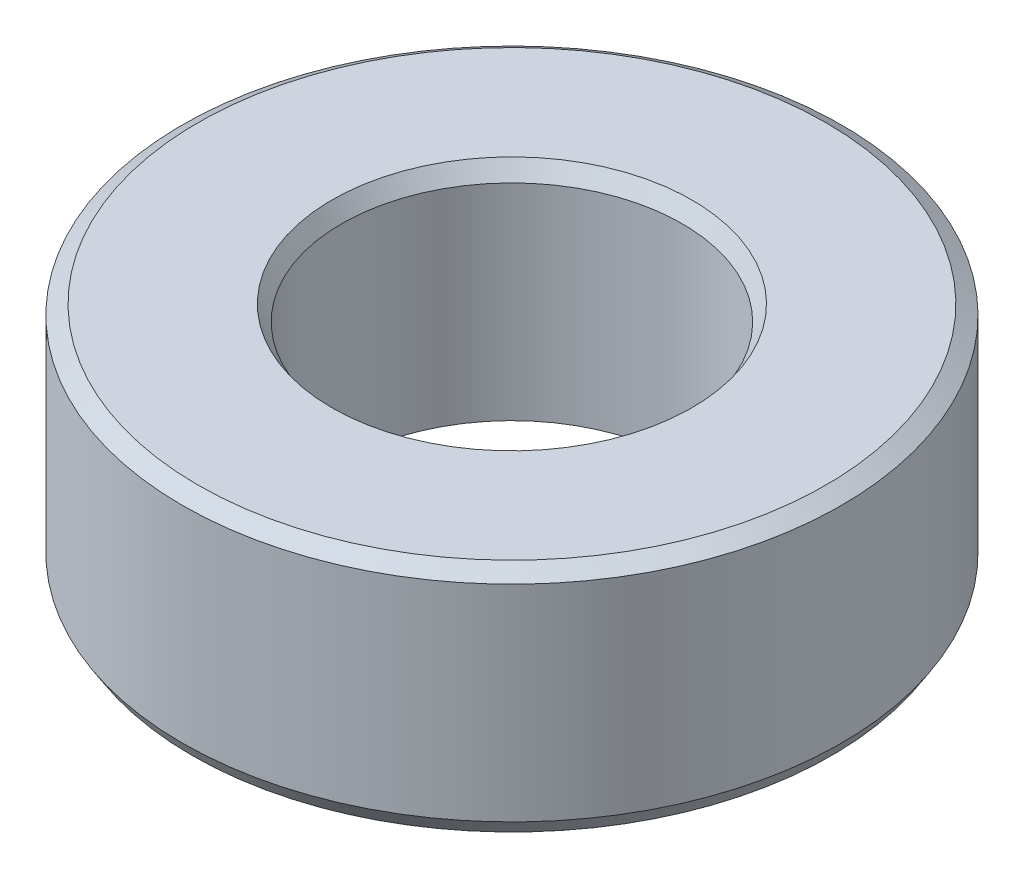
SolidWorks part; units mm, degrees
ref_plane "Front Plane" through (0, 0, 0) normal (0, 0, 1) x (1, 0, 0)
ref_plane "Top Plane" through (0, 0, 0) normal (0, 1, 0) x (1, 0, 0)
ref_plane "Right Plane" through (0, 0, 0) normal (1, 0, 0) x (0, 0, -1)
sketch "Sketch1" plane through (0, 0, 0) normal (0, 1, 0) x (1, 0, 0)
  circle A0 centre (0, 0) radius 50
  dimension "SLEEVE_OD" = 100
extrude "Boss-Extrude1" add sketch "Sketch1" along normal blind 35.0864
sketch "Sketch2" plane through (0, 0, 0) normal (0, 1, 0) x (1, 0, 0)
  circle A0 centre (0, 0) radius 25.8321
  dimension "BORE_D" = 51.6641
extrude "Cut-Extrude1" cut sketch "Sketch2" along normal through all
chamfer "Chamfer1" distance 1.4798 angle 58.063 4 edges at (0, 35.0864, 25.8321) (0, 0, 25.8321) (0, 0, 50) (0, 35.0864, 50) first distance on face at (0, 35.0864, 25.8321) first distance on face at (0, 0, 25.8321) first distance on face at (0, 35.0864, 50)
